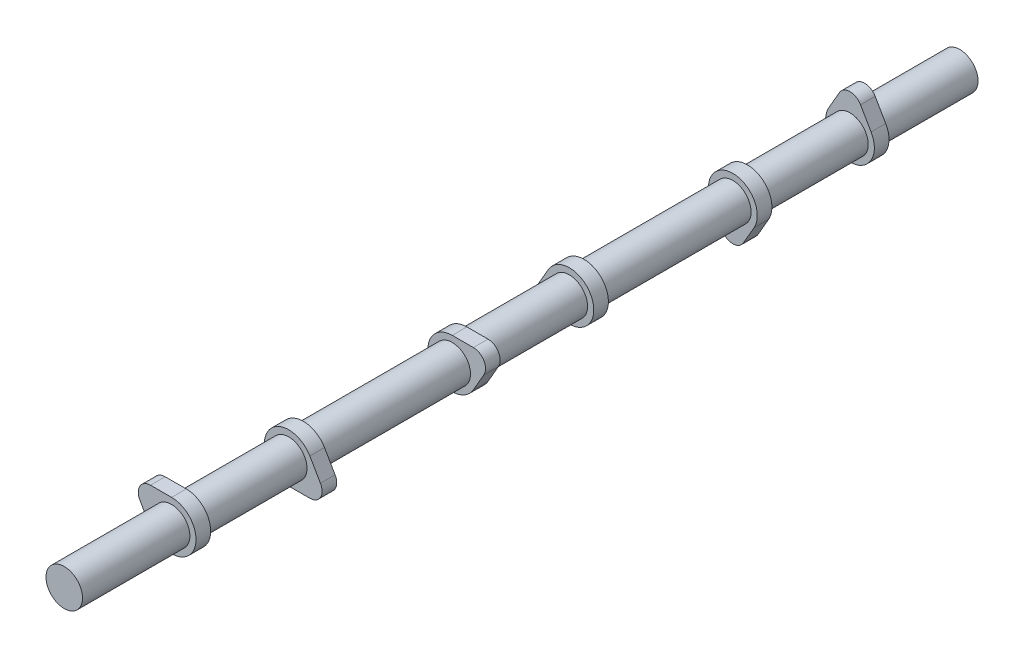
SolidWorks part; units mm, degrees
material "Alloy Steel"
ref_plane "Front Plane" through (0, 0, 0) normal (0, 0, 1) x (1, 0, 0)
ref_plane "Top Plane" through (0, 0, 0) normal (0, 1, 0) x (1, 0, 0)
ref_plane "Right Plane" through (0, 0, 0) normal (1, 0, 0) x (0, 0, -1)
sketch "Sketch1" plane through (0, 0, 0) normal (0, 0, 1) x (1, 0, 0)
  line L0 (-5.4993, 15.875) -> (-10.9985, 6.35)
  line L1 (5.4993, 15.875) -> (10.9985, 6.35)
  arc A0 (-10.9985, 6.35) -> (10.9985, 6.35) centre (0, 0) ccw
  arc A1 (5.4993, 15.875) -> (-5.4993, 15.875) centre (0, 12.7) ccw
  dimension "D1" = 25.4
  dimension "D2" = 12.7
  dimension "D3" = 12.7
extrude "Boss-Extrude1" add sketch "Sketch1" along normal mid plane 7.62
ref_axis "Axis1" through (0, 0, 88.0562) along (0, 0, -1)
pattern_linear "LPattern1" count 2 spacing 60.96 along (0, 0, 1) of bodies 101
move or copy body "Body-Move/Copy1" bodies to move or copy 102 copy no rotation origin (0, 0, 0) rotation axis (0, 0, 1) rotation angle 180
pattern_linear "LPattern2" count 3 spacing 146.05 along (0, 0, 1) of bodies 101 103
move or copy body "Body-Move/Copy2" bodies to move or copy 106 104 copy no rotation origin (0, 0, 0) rotation axis (0, 0, 1) rotation angle 120
move or copy body "Body-Move/Copy3" bodies to move or copy 107 105 copy no rotation origin (0, 0, 0) rotation axis (0, 0, -1) rotation angle 120
sketch "Sketch2" plane through (0, 0, -3.81) normal (0, 0, -1) x (-1, 0, 0)
  circle A0 centre (0, 0) radius 9.5
  dimension "D1" = 19
extrude "Boss-Extrude2" add sketch "Sketch2" against normal blind 466.09 from offset 49.53
